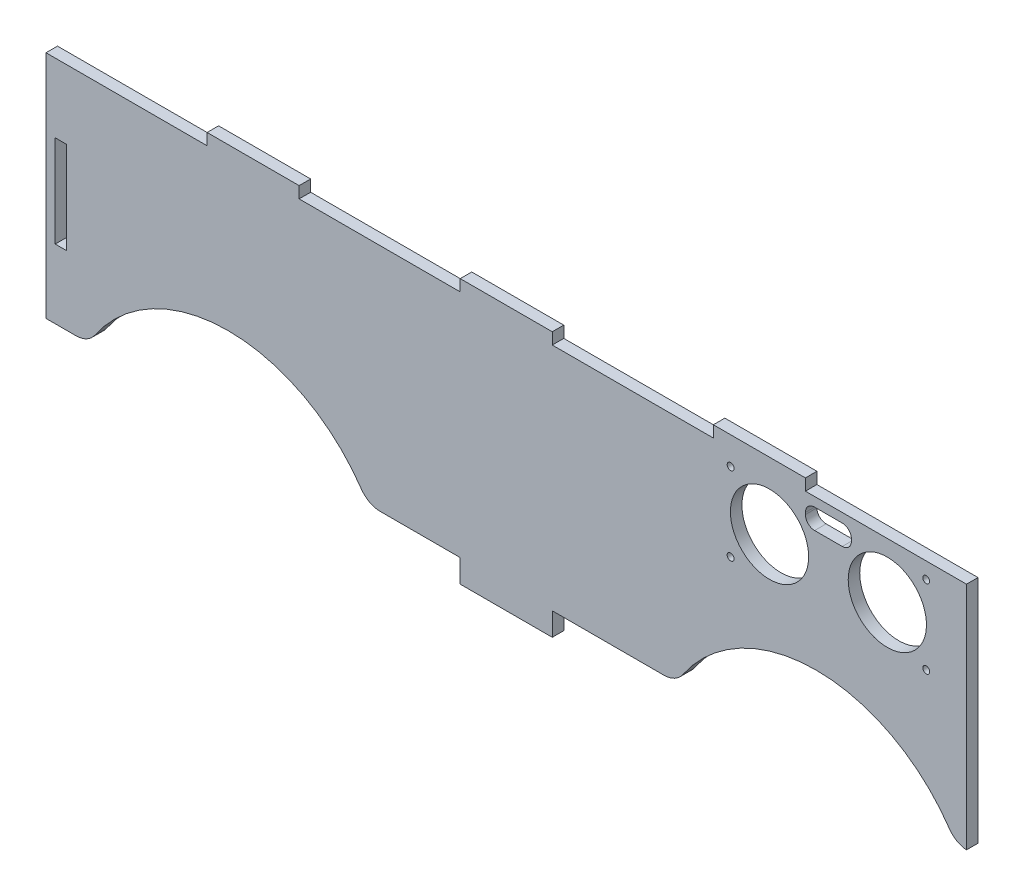
SolidWorks part; units mm, degrees
material "Maple"
ref_plane "Front Plane" through (0, 0, 0) normal (0, 0, 1) x (1, 0, 0)
ref_plane "Top Plane" through (0, 0, 0) normal (0, 1, 0) x (1, 0, 0)
ref_plane "Right Plane" through (0, 0, 0) normal (1, 0, 0) x (0, 0, -1)
sketch "Sketch1" plane through (0, 0, 0) normal (0, 0, 1) x (1, 0, 0)
  line L1 (-100, -25) -> (-100, 25) construction
  line L2 (0, -25) -> (0, 25) construction
  line L3 (-100, 25) -> (0, 25) construction
  line L4 (-100, -25) -> (0, 25) construction
  line L5 (0, -25) -> (-100, 25) construction
  line L6 (-102.5, 27.5) -> (0, 27.5) construction
  line L7 (30.1182, -25) -> (-30.1182, -25) construction
  line L8 (-102.5, -30) -> (6.0068, -30) construction
  line L9 (-102.5, -27.5) -> (-102.5, 27.5) construction
  line L10 (-98, -10) -> (-95.5, -10)
  line L11 (-98, -10) -> (-98, 10)
  line L12 (-98, 10) -> (-95.5, 10)
  line L13 (-95.5, -10) -> (-95.5, 10)
  line L14 (-98, -10) -> (-95.5, 10) construction
  line L15 (-98, 10) -> (-95.5, -10) construction
  line L16 (-90.74, -25) -> (-100, -25) construction
  line L17 (-100, -25) -> (-100, 25)
  line L18 (-100, 25) -> (-65, 25)
  line L19 (-65, 25) -> (-65, 27.5)
  line L20 (-65, 27.5) -> (-45, 27.5)
  line L21 (-45, 27.5) -> (-45, 25)
  line L22 (-45, 25) -> (-10, 25)
  line L23 (-10, 25) -> (-10, 27.5)
  line L24 (-10, 27.5) -> (10, 27.5)
  line L29 (-10, -25) -> (-10, -30)
  line L30 (-10, -30) -> (10, -30)
  line L35 (10, 25) -> (10, 27.5)
  line L36 (45, 25) -> (10, 25)
  line L37 (45, 27.5) -> (45, 25)
  line L38 (65, 27.5) -> (45, 27.5)
  line L39 (65, 25) -> (65, 27.5)
  line L40 (100, 25) -> (65, 25)
  line L41 (100, -25) -> (100, 25)
  line L44 (10, -30) -> (10, -25)
  line L56 (-10, -25) -> (-30.1182, -25)
  line L57 (-100, -25) -> (0, -25) construction
  line L58 (-90.74, -25) -> (-100, -25)
  line L60 (36.9982, -25) -> (10, -25)
  line L61 (-102.5, -27.5) -> (0, -27.5) construction
  line L62 (-25.3582, -25) -> (-25.3582, -10) construction
  line L63 (32.2382, -25) -> (32.2382, -7.347) construction
  line L64 (97.62, -25) -> (100, -25)
  line L65 (70, 22.8293) -> (70, 3.1707) construction
  line L66 (41.6502, 13) -> (98.3498, 13) construction
  line L67 (47.25, 3) -> (92.75, 3) construction
  line L68 (47.25, 3) -> (47.25, 23) construction
  line L69 (47.25, 23) -> (92.75, 23) construction
  line L70 (92.75, 3) -> (92.75, 23) construction
  line L71 (47.25, 3) -> (92.75, 23) construction
  line L72 (47.25, 23) -> (92.75, 3) construction
  line L73 (65, 18.6) -> (75, 18.6) construction
  line L74 (65, 18.6) -> (65, 23) construction
  line L75 (65, 23) -> (75, 23) construction
  line L76 (75, 18.6) -> (75, 23) construction
  line L77 (65, 18.6) -> (75, 23) construction
  line L78 (65, 23) -> (75, 18.6) construction
  line L79 (67, 18.6) -> (73, 18.6)
  line L80 (65, 20.6) -> (65, 21)
  line L81 (67, 23) -> (73, 23)
  line L82 (75, 20.6) -> (75, 21)
  line L83 (65, 18.6) -> (75, 23) construction
  line L84 (65, 23) -> (75, 18.6) construction
  arc A0 (-90.74, -25) -> (-30.1182, -25) centre (-60.4291, -42.5) cw
  arc A2 (36.9982, -25) -> (97.62, -25) centre (67.3091, -42.5) cw
  circle A3 centre (57.2, 13) radius 8.5
  circle A4 centre (48.75, 4.5) radius 0.75
  circle A5 centre (91.25, 4.5) radius 0.75
  circle A6 centre (82.8, 13) radius 8.5
  circle A7 centre (91.25, 21.5) radius 0.75
  circle A8 centre (48.75, 21.5) radius 0.75
  arc A9 (73, 23) -> (75, 21) centre (73, 21) cw
  arc A10 (65, 21) -> (67, 23) centre (67, 21) cw
  arc A11 (67, 18.6) -> (65, 20.6) centre (67, 20.6) cw
  arc A12 (73, 18.6) -> (75, 20.6) centre (73, 20.6) ccw
  point P0 (-96.75, 0)
  point P1 (-50, 0)
  point P42 (0, -30)
  point P65 (70, 13)
  point P70 (70, 20.8)
  point P75 (70, 20.8)
  dimension "D6" = 35
  dimension "D11" = 2.38
  dimension "D16" = 35
  dimension "D18" = 1.5
  dimension "D20" = 2
  dimension "D26" = 17
  dimension "D1" = 50
  dimension "D2" = 2.5
  dimension "D3" = 20
  dimension "D4" = 2.5
  dimension "D5" = 2
  dimension "D7" = 9.26
  dimension "D8" = 200
  dimension "D9" = 5
  dimension "D10" = 20
  dimension "D12" = 12.5
  dimension "D13" = 4.76
  dimension "D14" = 12.5
  dimension "D15" = 4.76
  dimension "D17" = 25.6
  dimension "D19" = 20
  dimension "D21" = 10
  dimension "D22" = 4.4
  dimension "D23" = 12
  dimension "D24" = 30
  dimension "D25" = 17
  dimension "D27" = 45.5
  dimension "D28" = 42.5
extrude "Boss-Extrude1" add sketch "Sketch1" along normal mid plane 2.5
fillet "Fillet2" radius 5 4 edges at (97.62, -25, 0) (36.9982, -25, 0) (-30.1182, -25, 0) (-90.74, -25, 0)
sketch "Sketch2" plane through (0, 0, -1.25) normal (0, 0, -1) x (-1, 0, 0)
  line L0 (-100, -25) -> (-100, 25) construction
  line L1 (-21.2, -7.05) -> (-8.2, -7.05)
  line L2 (-21.2, -7.05) -> (-21.2, -18.85)
  line L3 (-21.2, -18.85) -> (-8.2, -18.85)
  line L4 (-8.2, -7.05) -> (-8.2, -18.85)
  line L5 (-21.2, -7.05) -> (-8.2, -18.85) construction
  line L6 (-21.2, -18.85) -> (-8.2, -7.05) construction
  line L7 (-10, -25) -> (-34.2372, -25) construction
  line L9 (10.01, -18.85) -> (20.15, -18.85)
  line L10 (10.01, -18.85) -> (10.01, -7.05)
  line L11 (10.01, -7.05) -> (20.15, -7.05)
  line L12 (20.15, -18.85) -> (20.15, -7.05)
  line L13 (10.01, -18.85) -> (20.15, -7.05) construction
  line L14 (10.01, -7.05) -> (20.15, -18.85) construction
  point P0 (-14.7, -12.95)
  point P9 (15.08, -12.95)
  dimension "D1" = 78.8
  dimension "D2" = 6.15
  dimension "D3" = 11.8
  dimension "D4" = 13
  dimension "D5" = 110.01
  dimension "D6" = 10.14
extrude "Cut-Extrude1" [suppressed] cut sketch "Sketch2" against normal blind 10 contours L9 L12 L11 L10 | L4 L1 L2 L3
